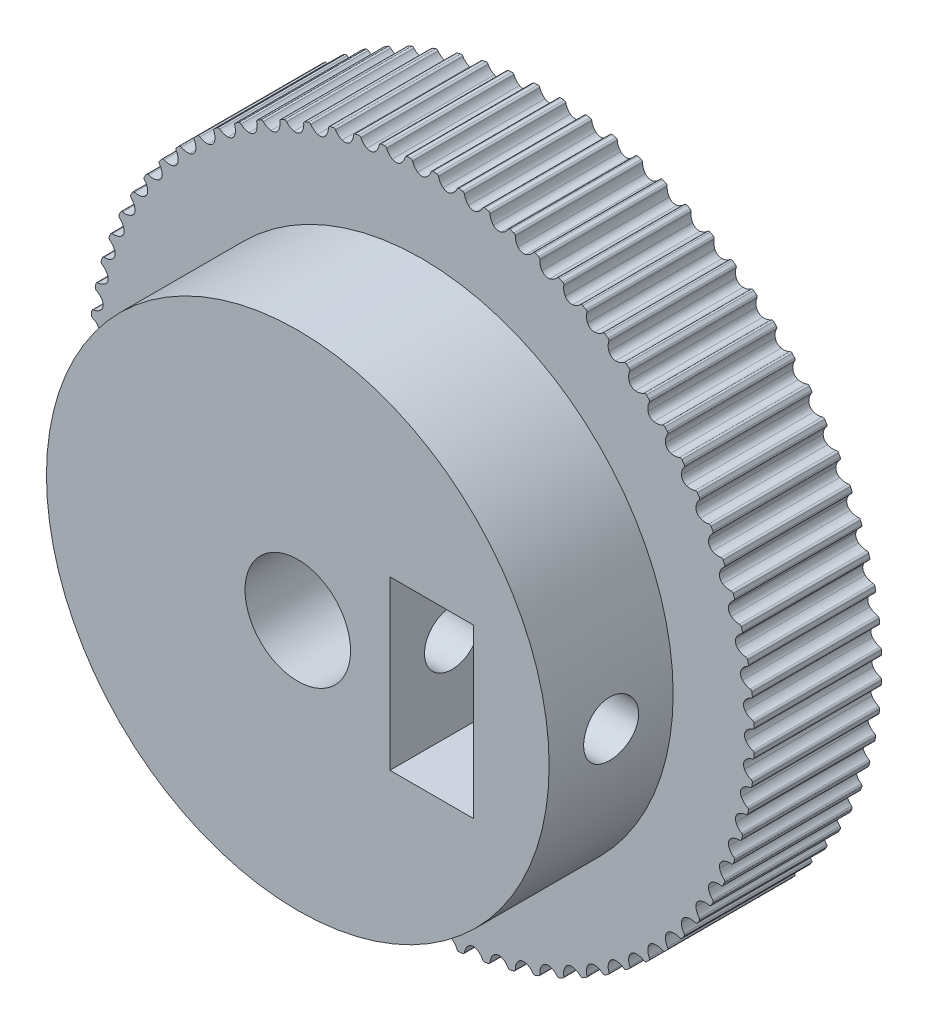
SolidWorks part; units mm, degrees
ref_plane "Front Plane" through (0, 0, 0) normal (0, 0, 1) x (1, 0, 0)
ref_plane "Top Plane" through (0, 0, 0) normal (0, 1, 0) x (1, 0, 0)
ref_plane "Right Plane" through (0, 0, 0) normal (1, 0, 0) x (0, 0, -1)
sketch "Sketch1" plane through (0, 0, 0) normal (0, 0, 1) x (1, 0, 0)
  line L3 (0, 25.2095) -> (1.9984, 25.1302) construction
  line L4 (0, 0) -> (0, 24.4595) construction
  line L5 (0, 24.4595) -> (0, 25.741) construction
  line L15 (1.9984, 25.1302) -> (2.047, 25.741)
  line L16 (2.047, 25.741) -> (-2.047, 25.741)
  line L17 (0, 24.4595) -> (0.1538, 24.4595) construction
  line L18 (-1.9984, 25.1302) -> (-2.047, 25.741)
  circle A0 centre (0, 0) radius 25.4635 construction
  circle A1 centre (0, 0) radius 25.2095 construction
  circle A2 centre (0, 0) radius 24.9555 construction
  arc A10 (0.8513, 25.1951) -> (1.9984, 25.1302) centre (0, 0) cw
  arc A11 (-0.3168, 24.5588) -> (0.3168, 24.5588) centre (0, 25.0145) ccw
  arc A12 (0.3168, 24.5588) -> (0.7027, 25.0889) centre (-0.254, 25.3799) ccw
  arc A13 (0.7027, 25.0889) -> (0.8513, 25.1951) centre (0.8462, 25.0452) cw
  arc A14 (-0.8513, 25.1951) -> (-1.9984, 25.1302) centre (0, 0) ccw
  arc A15 (-0.7027, 25.0889) -> (-0.8513, 25.1951) centre (-0.8462, 25.0452) ccw
  arc A16 (-0.3168, 24.5588) -> (-0.7027, 25.0889) centre (0.254, 25.3799) cw
  point P11 (0, 25.4635)
  point P13 (0, 25.2095)
  point P14 (0, 24.9555)
  dimension "D2" = 0.2775
sketch "Sketch2" plane through (0, 0, 0) normal (1, 0, 0) x (0, 0, -1)
  line L0 (-9.525, 4) -> (9.525, 4)
  line L1 (-9.525, 4) -> (-9.525, 19.05)
  line L2 (-9.525, 19.05) -> (-0.125, 19.05)
  line L3 (-0.125, 19.05) -> (-0.125, 25.2095)
  line L9 (9.525, 25.2095) -> (9.525, 4)
  line L10 (-9.525, 0) -> (9.525, 0) construction
  line L16 (-0.125, 25.2095) -> (9.525, 25.2095)
  point P25 (9.525, 0)
  point P26 (-0.125, 0)
  dimension "OA" = 19.05
  dimension "Bore" = 8
  dimension "Hub Dia" = 38.1
  dimension "Outside Width" = 9.65
revolve "Revolve1" add sketch "Sketch2" angle 360 mid plane about L10
sketch "Sketch3" plane through (0, 0, 0) normal (0, 0, 1) x (1, 0, 0)
  line L3 (1.9984, 25.1302) -> (2.047, 25.741) construction
  line L4 (-1.9984, 25.1302) -> (-2.047, 25.741) construction
  line L5 (2.047, 25.741) -> (-2.047, 25.741) construction
  line L6 (1.9984, 25.1302) -> (2.047, 25.741)
  line L7 (-1.9984, 25.1302) -> (-2.047, 25.741)
  line L8 (2.047, 25.741) -> (-2.047, 25.741)
  arc A0 (1.9984, 25.1302) -> (0.8513, 25.1951) centre (0, 0) ccw construction
  arc A1 (0.8513, 25.1951) -> (0.7027, 25.0889) centre (0.8462, 25.0452) ccw construction
  arc A3 (0.3168, 24.5588) -> (0.7027, 25.0889) centre (-0.254, 25.3799) ccw construction
  arc A4 (-0.3168, 24.5588) -> (0.3168, 24.5588) centre (0, 25.0145) ccw construction
  arc A5 (-0.7027, 25.0889) -> (-0.3168, 24.5588) centre (0.254, 25.3799) ccw construction
  arc A6 (-0.7027, 25.0889) -> (-0.8513, 25.1951) centre (-0.8462, 25.0452) ccw construction
  arc A7 (-0.8513, 25.1951) -> (-1.9984, 25.1302) centre (0, 0) ccw construction
  arc A8 (1.9984, 25.1302) -> (0.8513, 25.1951) centre (0, 0) ccw
  arc A9 (0.8513, 25.1951) -> (0.7027, 25.0889) centre (0.8462, 25.0452) ccw
  arc A10 (0.3168, 24.5588) -> (0.7027, 25.0889) centre (-0.254, 25.3799) ccw
  arc A11 (-0.3168, 24.5588) -> (0.3168, 24.5588) centre (0, 25.0145) ccw
  arc A12 (-0.7027, 25.0889) -> (-0.3168, 24.5588) centre (0.254, 25.3799) ccw
  arc A13 (-0.7027, 25.0889) -> (-0.8513, 25.1951) centre (-0.8462, 25.0452) ccw
  arc A14 (-0.8513, 25.1951) -> (-1.9984, 25.1302) centre (0, 0) ccw
extrude "Cut-Extrude1" cut sketch "Sketch3" against normal through all from surface starting at face at (19.05, 0, 0.125)
pattern_circular "CirPattern1" count 80 over 360 about axis through (0, 0, 9.525) along (0, 0, 1) of "Cut-Extrude1"
sketch "Sketch4" plane through (0, 0, 0) normal (1, 0, 0) x (0, 0, -1)
  line L0 (-9.525, 0) -> (-0.125, 0) construction
  line L1 (-9.525, 19.05) -> (-9.525, -19.05) construction
  line L2 (-0.125, 19.05) -> (-0.125, -19.05) construction
  circle A0 centre (-4.825, 0) radius 2.0828
  dimension "D1" = 4.1656
extrude "Cut-Extrude2" cut sketch "Sketch4" along normal through all
ref_plane "Plane1" through (0, 0, 4.825) normal (0, 0, 1) x (1, 0, 0)
sketch "Sketch5" plane through (0, 0, 4.825) normal (0, 0, 1) x (1, 0, 0)
  line L0 (3.415, -2.0828) -> (18.9358, -2.0828) construction
  line L1 (4.381, -2.0828) -> (18.5548, -2.0828)
  line L2 (18.9358, -1.7018) -> (18.9358, 0)
  line L3 (18.9358, 0) -> (4, 0) construction
  line L4 (4, -1.7018) -> (4, 0)
  line L5 (4.381, -2.0828) -> (4, -1.7018)
  line L6 (18.5548, -2.0828) -> (18.9358, -1.7018)
  line L13 (3.415, -2.0828) -> (18.9358, -2.0828) construction
  line L23 (4, 0) -> (18.9358, 0)
  circle A0 centre (0, 0) radius 19.05 construction
  circle A1 centre (0, 0) radius 4 construction
  point P0 (4, -2.0828)
  point P3 (18.9358, -2.0828)
  point P4 (-19.05, 0)
  point P6 (-4, 0)
ref_axis "Center Axis 1" through (0, 0, -9.525) along (0, 0, 1)
ref_plane "Contact Plane 1" through (0, 0, 9.525) normal (0, 0, 1) x (1, 0, 0)
ref_plane "Contact Plane 2" through (0, 0, -9.525) normal (0, 0, -1) x (-1, 0, 0)
sketch "Sketch6" plane through (0, 0, 9.525) normal (0, 0, 1) x (1, 0, 0)
  line L1 (6.985, 6.35) -> (13.335, 6.35)
  line L2 (6.985, 6.35) -> (6.985, -6.35)
  line L3 (6.985, -6.35) -> (13.335, -6.35)
  line L4 (13.335, 6.35) -> (13.335, -6.35)
  line L5 (6.985, 6.35) -> (13.335, -6.35) construction
  line L6 (6.985, -6.35) -> (13.335, 6.35) construction
  point P4 (10.16, 0)
  point P5 (0, 0)
  dimension "D1" = 6.35
  dimension "D2" = 12.7
  dimension "D3" = 10.16
extrude "Cut-Extrude3" cut sketch "Sketch6" against normal blind 12.7
equation "\"D2@Sketch1\" = \"R3@Sketch1\"/2"
